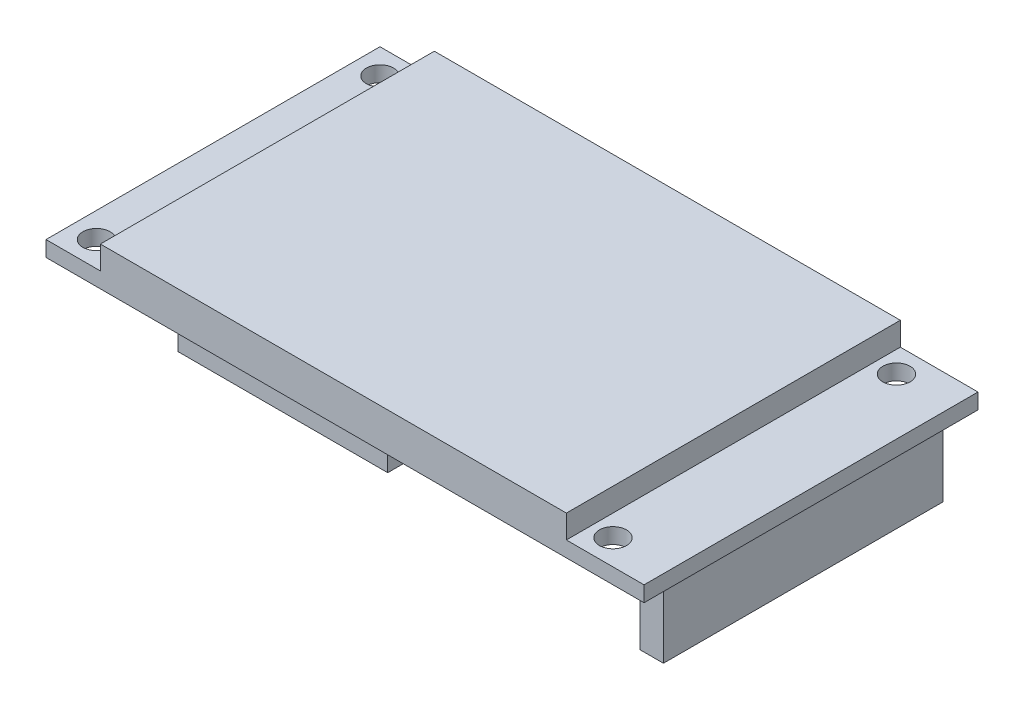
SolidWorks part; units mm, degrees
ref_plane "Front Plane" through (0, 0, 0) normal (0, 0, 1) x (1, 0, 0)
ref_plane "Top Plane" through (0, 0, 0) normal (0, 1, 0) x (1, 0, 0)
ref_plane "Right Plane" through (0, 0, 0) normal (1, 0, 0) x (0, 0, -1)
sketch "Sketch1" plane through (0, 0, 0) normal (0, 1, 0) x (1, 0, 0)
  line L1 (-38.5, 21.5) -> (38.5, 21.5)
  line L2 (-38.5, 21.5) -> (-38.5, -21.5)
  line L3 (-38.5, -21.5) -> (38.5, -21.5)
  line L4 (38.5, 21.5) -> (38.5, -21.5)
  line L5 (-38.5, 21.5) -> (38.5, -21.5) construction
  line L6 (-38.5, -21.5) -> (38.5, 21.5) construction
  line L7 (-31.5, 21.5) -> (28.5, 21.5)
  line L8 (-31.5, 21.5) -> (-31.5, -21.5)
  line L9 (-31.5, -21.5) -> (28.5, -21.5)
  line L10 (28.5, 21.5) -> (28.5, -21.5)
  line L11 (-31.5, 21.5) -> (28.5, -21.5) construction
  line L12 (-31.5, -21.5) -> (28.5, 21.5) construction
  point P0 (0, 0)
  point P6 (-1.5, 0)
  dimension "D1" = 43
  dimension "D2" = 77
  dimension "D3" = 0
  dimension "D4" = 43
  dimension "D5" = 10
  dimension "D6" = 7
  dimension "D7" = 60
extrude "Boss-Extrude1" add sketch "Sketch1" along normal blind 5 contours L10 L1 L8 L3 region at (-1.5, 0, 0)
extrude "Boss-Extrude2" add sketch "Sketch1<3>" along normal blind 2 contours L1 L10 L3 L4 | L8 L1 L2 L3 region at (-35, 0, 0) region at (33.5, 0, 0)
sketch "Sketch1<3>" plane through (0, 0, 0) normal (0, 1, 0) x (1, 0, 0) same geometry as "Sketch1"
sketch "Sketch2" plane through (0, 2, 0) normal (0, 1, 0) x (1, 0, 0)
  line L0 (28.5, 21.5) -> (38.5, 21.5) construction
  line L1 (38.5, 21.5) -> (38.5, -21.5) construction
  line L2 (28.5, -21.5) -> (38.5, -21.5) construction
  circle A0 centre (31.25, 18.25) radius 1.75
  circle A1 centre (31.25, -18.25) radius 1.75
  dimension "D1" = 3.5
  dimension "D4" = 3.5
  dimension "D5" = 7.25
  dimension "D6" = 3.25
  dimension "D7" = 36.5
  dimension "D2" = 3.25
  dimension "D3" = 7.25
extrude "Cut-Extrude1" cut sketch "Sketch2" against normal blind 2
sketch "Sketch3" plane through (0, 2, 0) normal (0, 1, 0) x (1, 0, 0)
  line L0 (-38.5, 21.5) -> (-38.5, -21.5) construction
  line L1 (-38.5, 21.5) -> (-31.5, 21.5) construction
  line L2 (-38.5, -21.5) -> (-31.5, -21.5) construction
  circle A0 centre (-35.25, 18.25) radius 1.75
  circle A1 centre (-35.25, -18.25) radius 1.75
  dimension "D1" = 3.5
  dimension "D2" = 3.5
  dimension "D4" = 3.25
  dimension "D6" = 3.25
  dimension "D7" = 36.5
  dimension "D3" = 3.25
  dimension "D5" = 3.25
extrude "Cut-Extrude2" cut sketch "Sketch3" against normal blind 2
sketch "Sketch4" plane through (0, 0, 0) normal (0, -1, 0) x (1, 0, 0)
  line L0 (-38.5, 21.5) -> (38.5, 21.5) construction
  line L1 (34.5, 18) -> (37.5, 18)
  line L2 (34.5, 18) -> (34.5, -18)
  line L3 (34.5, -18) -> (37.5, -18)
  line L4 (37.5, 18) -> (37.5, -18)
  line L5 (34.5, 18) -> (37.5, -18) construction
  line L6 (34.5, -18) -> (37.5, 18) construction
  line L7 (-38.5, -21.5) -> (38.5, -21.5) construction
  line L8 (38.5, -21.5) -> (38.5, 21.5) construction
  point P0 (36, 0)
  dimension "D1" = 36
  dimension "D2" = 3
  dimension "D3" = 3.5
  dimension "D4" = 3.5
  dimension "D5" = 1
extrude "Boss-Extrude3" add sketch "Sketch4" along normal blind 9
sketch "Sketch5" plane through (0, 0, 0) normal (0, -1, 0) x (1, 0, 0)
  line L0 (-38.5, -21.5) -> (-38.5, 21.5) construction
  line L1 (-22.5, 20.5) -> (4.5, 20.5)
  line L2 (-22.5, 20.5) -> (-22.5, 2.5)
  line L3 (-22.5, 2.5) -> (4.5, 2.5)
  line L4 (4.5, 20.5) -> (4.5, 2.5)
  line L5 (-22.5, 20.5) -> (4.5, 2.5) construction
  line L6 (-22.5, 2.5) -> (4.5, 20.5) construction
  line L7 (-38.5, 21.5) -> (38.5, 21.5) construction
  point P0 (-9, 11.5)
  dimension "D1" = 18
  dimension "D2" = 27
  dimension "D3" = 16
  dimension "D4" = 1
extrude "Boss-Extrude4" add sketch "Sketch5" along normal blind 3
